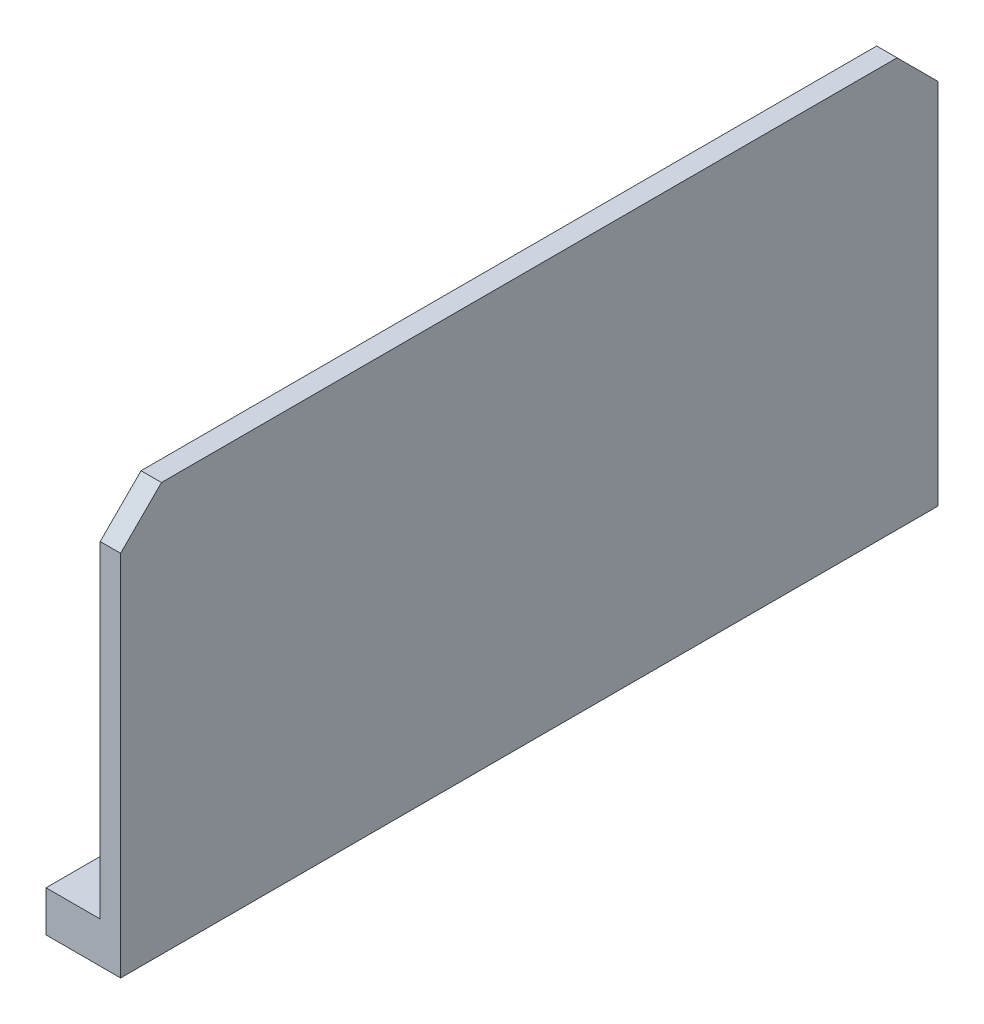
SolidWorks part; units mm, degrees
ref_plane "前视基准面" through (0, 0, 0) normal (0, 0, 1) x (1, 0, 0)
ref_plane "上视基准面" through (0, 0, 0) normal (0, 1, 0) x (1, 0, 0)
ref_plane "右视基准面" through (0, 0, 0) normal (1, 0, 0) x (0, 0, -1)
other "Configuration Table"
sketch "草图1" plane through (0, 0, 0) normal (0, 1, 0) x (1, 0, 0)
  line L0 (0, 35) -> (0, -35) construction
  line L2 (-2.4, 40) -> (2.4, 40)
  line L3 (-2.4, 40) -> (-2.4, -40)
  line L4 (-2.4, -40) -> (2.4, -40)
  line L5 (2.4, 40) -> (2.4, -40)
  line L6 (-2.4, 40) -> (2.4, -40) construction
  line L7 (-2.4, -40) -> (2.4, 40) construction
  line L8 (2.4, 40) -> (2.9, 40)
  line L9 (2.4, 40) -> (2.4, -40)
  line L10 (2.4, -40) -> (2.9, -40)
  line L11 (2.9, 40) -> (2.9, -40)
  line L12 (-2.4, -30) -> (2.4, -30)
  line L13 (-2.4, -30) -> (-2.4, 30)
  line L14 (-2.4, 30) -> (2.4, 30)
  line L15 (2.4, -30) -> (2.4, 30)
  line L16 (-2.4, -30) -> (2.4, 30) construction
  line L17 (-2.4, 30) -> (2.4, -30) construction
  line L18 (2.9, -40) -> (4.9, -40)
  line L19 (2.9, -40) -> (2.9, 40)
  line L20 (2.9, 40) -> (4.9, 40)
  line L21 (4.9, -40) -> (4.9, 40)
  circle A0 centre (0, -35) radius 1.5
  circle A1 centre (0, 35) radius 1.5
  point P4 (0, 0)
  point P7 (0, 0)
  point P15 (0, 0)
  dimension "D1" = 3
  dimension "D2" = 70
  dimension "D3" = 4.8
  dimension "D4" = 80
  dimension "D5" = 0.5
  dimension "D6" = 60
  dimension "D7" = 2
extrude "凸台-拉伸1" add sketch "草图1" along normal blind 4 contours L12 L3 L4 L9 A0 | L14 L3 L12 L9 | L3 L14 L5 L2 A1 | L11 L8 L5 L9 L10 | L18 L21 L20 L11 region at (0, 0, -39.8891) region at (2.65, 0, 0) region at (0, 0, 0) region at (3.9, 0, 0) region at (0, 0, 30.1109)
extrude "凸台-拉伸3" add sketch "草图1<4>" along normal blind 40 contours L18 L21 L20 L11 region at (3.9, 0, 0)
sketch "草图1<4>" plane through (0, 0, 0) normal (0, 1, 0) x (1, 0, 0) same geometry as "草图1"
sketch "草图2" plane through (0, 0, 0) normal (0, 0, 1) x (1, 0, 0)
  line L0 (2.9, 4) -> (-7.1, 4)
  line L1 (-7.1, 4) -> (2.9, 40)
  line L2 (2.9, 40) -> (2.9, 4)
  line L3 (-2.4, 0) -> (4.9, 0) construction
  line L4 (2.9, 4) -> (-7.1, 4)
  line L5 (2.9, 4) -> (2.9, 0)
  line L6 (2.9, 0) -> (-7.1, 0)
  line L7 (-7.1, 4) -> (-7.1, 0)
  line L8 (2.9, 40) -> (2.9, 4) construction
  line L9 (-2.4, 4) -> (2.9, 4) construction
  point P12 (0, 0)
  point P13 (2.9, 9.6703)
  dimension "D1" = 10
extrude "凸台-拉伸4" add sketch "草图2" along normal mid plane 2 contours L0 L7 L6 L5 | L0 L1 L2 region at (-2.1, 2, 0)
chamfer "倒角1" distance 4 angle 45 2 edges at (3.9, 40, 40) (3.9, 40, -40)
